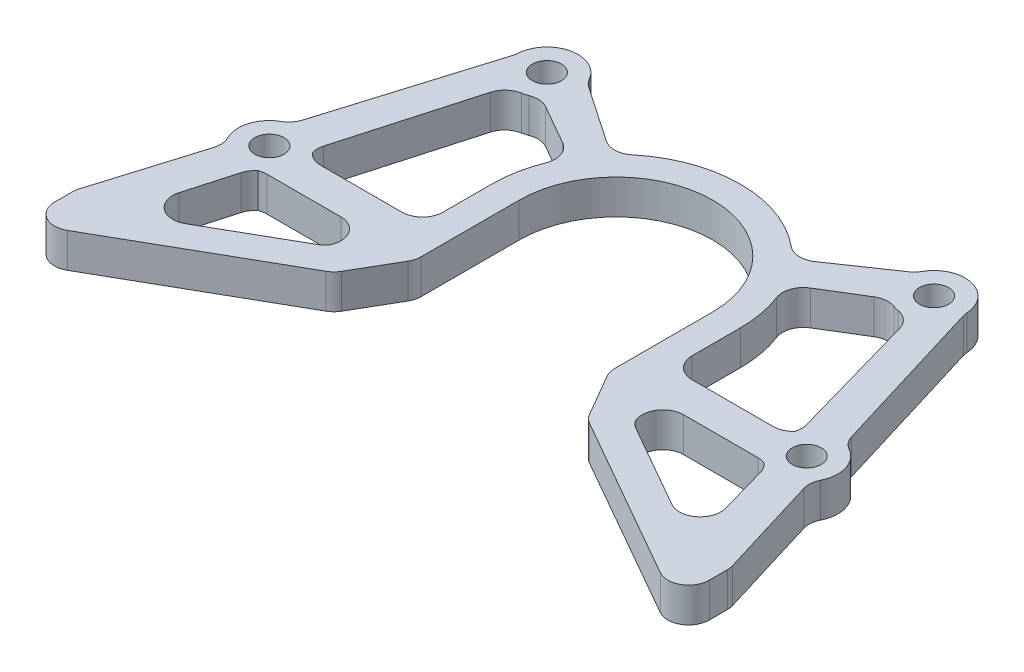
SolidWorks part; units mm, degrees
ref_plane "Front" through (0, 0, 0) normal (0, 0, 1) x (1, 0, 0)
ref_plane "Top" through (0, 0, 0) normal (0, 1, 0) x (1, 0, 0)
ref_plane "Right" through (0, 0, 0) normal (1, 0, 0) x (0, 0, -1)
sketch "Sketch1" plane through (0, 0, 0) normal (0, 1, 0) x (1, 0, 0)
  line L0 (0, -1.2821) -> (0, -50001.2821) construction
  line L5 (-25.2482, 14.4394) -> (-15.6252, 8.936)
  line L6 (-13.1084, 12.3357) -> (-23.8139, 19.6513)
  line L7 (13.1084, 12.3357) -> (23.8139, 19.6513)
  line L8 (25.2482, 14.4394) -> (15.7848, 8.651)
  line L30 (-41.5326, -30.7205) -> (-37.214, -15.4712)
  line L34 (-14, 0) -> (-14, -15)
  line L35 (14, 0) -> (14, -15)
  line L39 (-18, 0) -> (-18, -10)
  line L43 (18, 0) -> (18, -10)
  line L44 (-32.5, 18) -> (-40.096, -6.9562)
  line L46 (32.5, 18) -> (40.0949, -6.9525)
  line L47 (-18.3429, -22.4777) -> (-47.3572, -39.0304)
  line L48 (-47.3572, -39.0304) -> (-47.3572, -30.8122)
  line L49 (-22.3429, -19.7597) -> (-41.5326, -30.7205)
  line L50 (47.3572, -39.0304) -> (47.3572, -30.8122)
  line L52 (18.3429, -22.4777) -> (47.3572, -39.0304)
  line L57 (-22.3429, -19.7597) -> (-19.5786, -15)
  line L58 (-18.3429, -22.4777) -> (-14, -15)
  line L59 (18.3429, -22.4777) -> (14, -15)
  line L60 (22.3429, -19.7597) -> (19.5786, -15)
  line L61 (-36.324, -15) -> (-19.5786, -15)
  line L62 (18, -10) -> (34.5544, -10)
  line L63 (-34.5481, -10) -> (-18, -10)
  line L64 (-35.2628, -8.5813) -> (-28.979, 13.6078)
  line L65 (19.5786, -15) -> (36.3329, -15)
  line L66 (35.2644, -8.5867) -> (28.979, 13.6078)
  line L67 (41.5326, -30.7205) -> (37.2127, -15.4665)
  line L68 (22.3429, -19.7597) -> (41.5326, -30.7205)
  line L69 (-42.2975, -14.1889) -> (-47.3572, -30.8122)
  line L70 (42.2989, -14.1937) -> (47.3572, -30.8122)
  arc A0 (14, 0) -> (-14, 0) centre (0, 0) ccw
  circle A4 centre (-28, 18) radius 2.1
  circle A5 centre (28, 18) radius 2.1
  arc A12 (-28.979, 13.6078) -> (-25.2482, 14.4394) centre (-28, 18) ccw
  arc A13 (-23.8139, 19.6513) -> (-32.5, 18) centre (-28, 18) ccw
  arc A14 (28.979, 13.6078) -> (25.2482, 14.4394) centre (28, 18) cw
  arc A15 (23.8139, 19.6513) -> (32.5, 18) centre (28, 18) cw
  arc A24 (18, 0) -> (15.7848, 8.651) centre (0, 0) ccw
  arc A25 (13.1084, 12.3357) -> (-13.1084, 12.3357) centre (0, 0) ccw
  arc A26 (-15.6252, 8.936) -> (-18, 0) centre (0, 0) ccw
  circle A29 centre (-38.8612, -11.2835) radius 2.1
  circle A31 centre (38.8679, -11.282) radius 2.1
  arc A33 (-40.096, -6.9562) -> (-42.2975, -14.1889) centre (-38.8612, -11.2835) ccw
  arc A34 (35.2644, -8.5867) -> (34.5544, -10) centre (38.8679, -11.282) ccw
  arc A35 (-37.214, -15.4712) -> (-36.324, -15) centre (-38.8612, -11.2835) ccw
  arc A36 (-34.5481, -10) -> (-35.2628, -8.5813) centre (-38.8612, -11.2835) ccw
  arc A37 (36.3329, -15) -> (37.2127, -15.4665) centre (38.8679, -11.282) ccw
  arc A38 (42.2989, -14.1937) -> (40.0949, -6.9525) centre (38.8679, -11.282) ccw
  point P23 (0, 18)
  dimension "D2" = 56
extrude "Boss-Extrude1" add sketch "Sketch1" along normal blind 5
fillet "Fillet1" radius 3 40 edges at (-23.8139, 2.5, -19.6513) (23.8139, 2.5, -19.6513) (-25.2482, 2.5, -14.4394) (25.2482, 2.5, -14.4394) (15.7848, 2.5, -8.651) (-15.6252, 2.5, -8.936) (-22.3429, 2.5, 19.7597) (47.3572, 2.5, 39.0304) (18.3429, 2.5, 22.4777) (14, 2.5, 15) (-18.3429, 2.5, 22.4777) (-47.3572, 2.5, 39.0304) (-32.5, 2.5, -18) (-13.1084, 2.5, -12.3357) (13.1084, 2.5, -12.3357) (32.5, 2.5, -18) (-14, 2.5, 15) (-28.979, 2.5, -13.6078) (-18, 2.5, 10) (19.5786, 2.5, 15) (-19.5786, 2.5, 15) (18, 2.5, 10) (28.979, 2.5, -13.6078) (47.3572, 2.5, 30.8122) (-47.3572, 2.5, 30.8122) (-42.2975, 2.5, 14.1889) (-40.096, 2.5, 6.9562) (40.0949, 2.5, 6.9525) (42.2989, 2.5, 14.1937) (37.2127, 2.5, 15.4665) (36.3329, 2.5, 15) (22.3429, 2.5, 19.7597) (41.5326, 2.5, 30.7205) (34.5544, 2.5, 10) (35.2644, 2.5, 8.5867) (-35.2628, 2.5, 8.5813) (-34.5481, 2.5, 10) (-36.324, 2.5, 15) (-41.5326, 2.5, 30.7205) (-37.214, 2.5, 15.4712)
